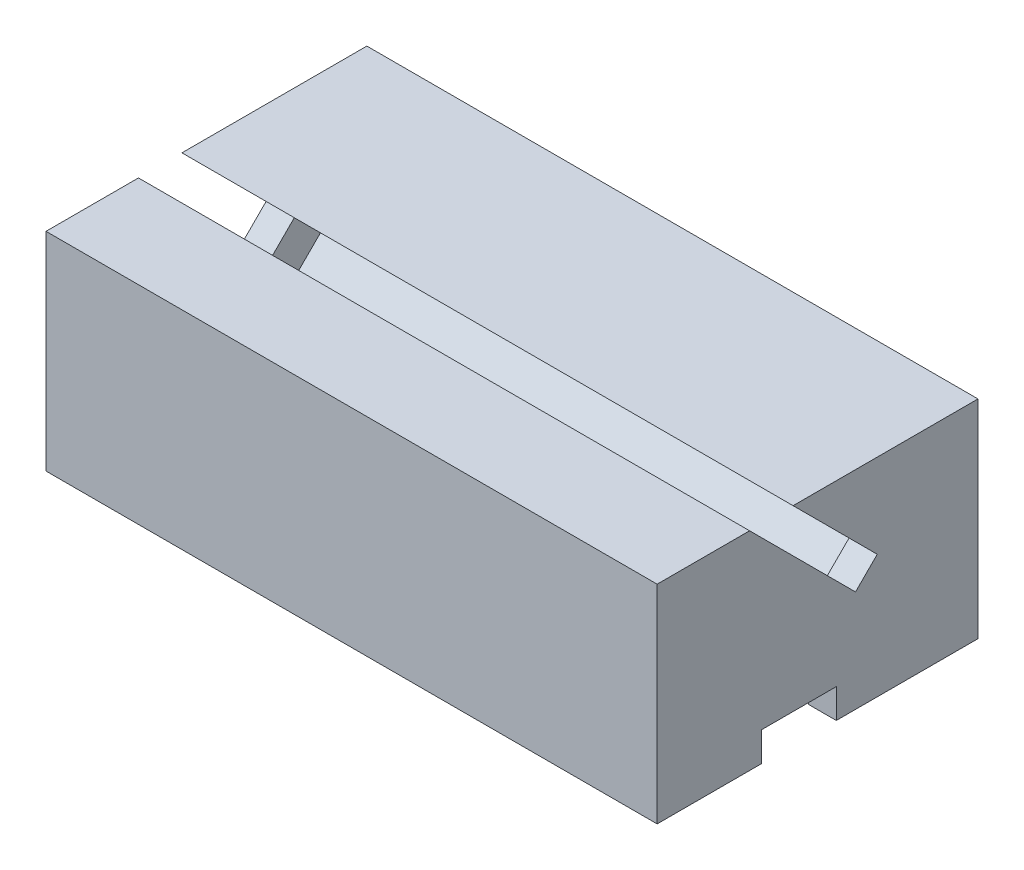
SolidWorks part; units mm, degrees
ref_plane "Front Plane" through (0, 0, 0) normal (0, 0, 1) x (1, 0, 0)
ref_plane "Top Plane" through (0, 0, 0) normal (0, 1, 0) x (1, 0, 0)
ref_plane "Right Plane" through (0, 0, 0) normal (1, 0, 0) x (0, 0, -1)
sketch "Sketch1" plane through (0, 0, 0) normal (1, 0, 0) x (0, 0, -1)
  line L0 (0, 0) -> (0, 19.2836)
  line L1 (0, 19.2836) -> (10, 19.2836)
  line L2 (34.7023, 19.2836) -> (34.7023, 0)
  line L3 (34.7023, 0) -> (0, 0)
  line L4 (10, 19.2836) -> (24.2836, 5)
  line L5 (24.2836, 5) -> (26.6347, 7.3511)
  line L6 (26.6347, 7.3511) -> (14.7023, 19.2836)
  line L7 (23.8063, 10.1796) -> (21.4551, 7.8284)
  line L8 (14.7023, 19.2836) -> (34.7023, 19.2836)
  dimension "D2" = 20.2
  dimension "D3" = 3.325
  dimension "D4" = 10
  dimension "D5" = 20
  dimension "D6" = 5
  dimension "D7" = 4
  dimension "D1" = 45
extrude "Boss-Extrude1" add sketch "Sketch1" along normal blind 66.1 contours L8 L6 L5 L4 L1 L0 L3 L2 region at (0, 9.3303, -17.1988)
extrude "Boss-Extrude2" add sketch "Sketch1<4>" along normal blind 3.05 contours L6 L7 L4 L5 region at (0, 7.5898, -24.0449)
sketch "Sketch1<4>" plane through (0, 0, 0) normal (1, 0, 0) x (0, 0, -1) same geometry as "Sketch1"
ref_plane "Plane1" through (33.05, 0, 0) normal (-1, 0, 0) x (0, 0, 1)
mirror "Mirror1" about plane through (33.05, 0, 0) normal (-1, 0, 0) of "Boss-Extrude2"
sketch "Sketch2" plane through (0, 0, 0) normal (0, 1, 0) x (1, 0, 0)
  line L0 (0, 0) -> (0, 11.2761)
  line L1 (0, 0) -> (0, 10) construction
  line L2 (0, 11.2761) -> (3, 11.2761)
  line L3 (3, 11.2761) -> (3, 7.1761)
  line L4 (3, 7.1761) -> (63.1, 7.1761)
  line L5 (63.1, 7.1761) -> (63.1, 11.2761)
  line L6 (63.1, 11.2761) -> (66.1, 11.2761)
  line L7 (66.1, 0) -> (66.1, 10) construction
  line L8 (66.1, 11.2761) -> (66.1, 0)
  line L9 (66.1, 0) -> (0, 0)
  line L10 (0, 34.7023) -> (0, 19.3761)
  line L11 (0, 14.7023) -> (0, 34.7023) construction
  line L12 (0, 19.3761) -> (3, 19.3761)
  line L13 (3, 19.3761) -> (3, 27.5261)
  line L14 (3, 27.5261) -> (63.1, 27.5261)
  line L15 (63.1, 27.5261) -> (63.1, 19.3761)
  line L16 (63.1, 19.3761) -> (66.1, 19.3761)
  line L17 (66.1, 14.7023) -> (66.1, 34.7023) construction
  line L18 (66.1, 19.3761) -> (66.1, 34.7023)
  line L19 (66.1, 34.7023) -> (0, 34.7023)
  line L20 (33.05, 34.7376) -> (33.05, 0) construction
  line L21 (0, 17.3511) -> (66.1, 17.3511) construction
  line L23 (0, 34.7023) -> (0, 0) construction
  circle A0 centre (12.05, 14.1761) radius 1.5
  circle A1 centre (54.05, 14.1761) radius 1.5
  point P33 (33.05, 34.7023)
  point P38 (0, 17.3511)
  line M21 (0, 0) -> (0, 34.7023)
  line M22 (0, 34.7023) -> (66.1, 34.7023)
  line M23 (66.1, 34.7023) -> (66.1, 0)
  line M24 (66.1, 0) -> (0, 0)
  dimension "D9" = 3
  dimension "D1" = 3
  dimension "D2" = 8.1
  dimension "D3" = 4.1
  dimension "D4" = 8.15
  dimension "D5" = 3
  dimension "D7" = 12.05
  dimension "D8" = 7
extrude "Boss-Extrude3" add sketch "Sketch2" against normal blind 3.175 contours L5 L6 L2 L3 L4 M23 M24 M21 | L16 L15 L14 L13 L12 M21 M22 M23 region at (33.05, 0, -3.866) region at (33.05, 0, -30.398)
extrude "Cut-Extrude1" cut sketch "Sketch2<4>" along normal blind 3 contours A1 | A0 region at (12.05, 0, -14.1761) region at (54.05, 0, -14.1761)
sketch "Sketch2<4>" plane through (0, 0, 0) normal (0, 1, 0) x (1, 0, 0) same geometry as "Sketch2"
chamfer "Chamfer1" distance 1.5 angle 45 4 edges at (12.05, 3, -15.6761) (54.05, 3, -15.6761) (12.05, 0, -15.6761) (54.05, 0, -15.6761)
chamfer "Chamfer3" distance 3.175 angle 45 1 edges at (33.05, 0, -27.5261)
equation "\"D2@Sketch1\"=20.05 + 0.15"
equation "\"D3@Sketch1\"=3.175 + 0.15"
equation "\"D5@Sketch2\"=\"D1@Sketch2\""
equation "\"D2@Sketch2\"=8.00 + 0.10"
equation "\"D1@Sketch2\"=3.05 - 0.05"
equation "\"D4@Sketch2\"=8.05 + 0.10"
equation "\"D3@Sketch2\"=4.00 + 0.10"
